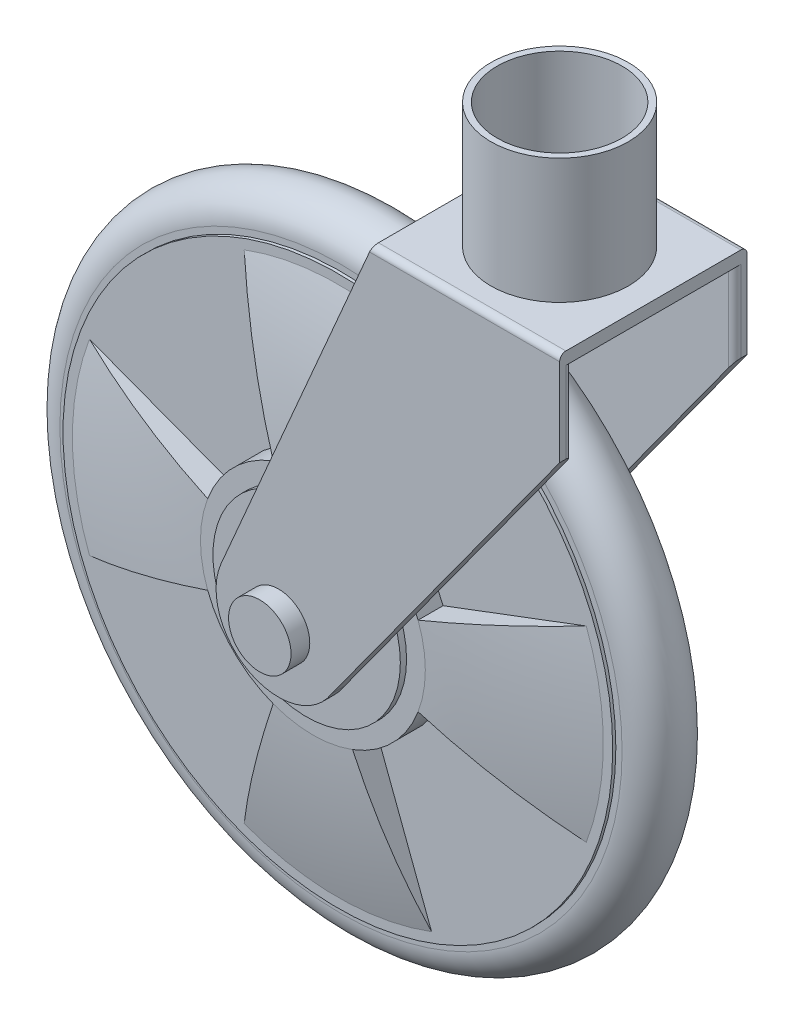
SolidWorks part; units mm, degrees
ref_plane "Plano frontal" through (0, 0, 0) normal (0, 0, 1) x (1, 0, 0)
ref_plane "Plano superior" through (0, 0, 0) normal (0, 1, 0) x (1, 0, 0)
ref_plane "Plano direito" through (0, 0, 0) normal (1, 0, 0) x (0, 0, -1)
sketch "Esboço1" plane through (0, 0, 0) normal (0, 1, 0) x (1, 0, 0)
  line L0 (0, 0) -> (-45, 0) construction
  line L1 (0, 0) -> (0, 36.2731) construction
  line L2 (-45, 5) -> (-44, 5)
  line L3 (-44, 5) -> (-44, 5.5)
  line L4 (-44, 5.5) -> (0, 5.5)
  line L5 (0, 5.5) -> (0, 0)
  line L6 (-45, -5) -> (-44, -5)
  line L7 (-44, -5) -> (-44, -5.5)
  line L8 (-44, -5.5) -> (0, -5.5)
  line L9 (0, 5.5) -> (0, -5.5)
  arc A0 (-45, 5) -> (-45, -5) centre (-45, 0) ccw
  point P7 (-44, 5.25)
  dimension "D1" = 10
  dimension "D2" = 45
  dimension "D3" = 0.5
  dimension "D4" = 1
revolve "Revolução3" add sketch "Esboço1" angle 360 about L1
sketch "Esboço3" plane through (0, 0, 5.5) normal (0, 0, 1) x (1, 0, 0)
  line L0 (0, 18) -> (0, 42.5) construction
  line L1 (-15, 39.7649) -> (-6.3529, 16.8416)
  line L2 (15, 39.7649) -> (6.3529, 16.8416)
  line L3 (39.7649, -15) -> (16.8416, -6.3529)
  line L4 (39.7649, 15) -> (16.8416, 6.3529)
  line L5 (-15, -39.7649) -> (-6.3529, -16.8416)
  line L6 (15, -39.7649) -> (6.3529, -16.8416)
  line L7 (-39.7649, 15) -> (-16.8416, 6.3529)
  line L8 (-39.7649, -15) -> (-16.8416, -6.3529)
  arc A0 (-16.8416, -6.3529) -> (-6.3529, -16.8416) centre (0, 0) ccw
  arc A1 (-39.7649, 15) -> (-39.7649, -15) centre (0, 0) ccw
  arc A2 (-15, -39.7649) -> (15, -39.7649) centre (0, 0) ccw
  arc A3 (15, 39.7649) -> (-15, 39.7649) centre (0, 0) ccw
  arc A4 (39.7649, -15) -> (39.7649, 15) centre (0, 0) ccw
  arc A5 (6.3529, -16.8416) -> (16.8416, -6.3529) centre (0, 0) ccw
  arc A6 (16.8416, 6.3529) -> (6.3529, 16.8416) centre (0, 0) ccw
  arc A7 (-6.3529, 16.8416) -> (-16.8416, 6.3529) centre (0, 0) ccw
  circle A8 centre (0, 0) radius 18 construction
  point P7 (0, 0)
  point P24 (0, 0)
  dimension "D1" = 36
  dimension "D2" = 85
  dimension "D3" = 15
  dimension "D4" = 4
extrude "Ressalto-extrusão1" add sketch "Esboço3" along normal blind 4
sketch "Esboço4" plane through (0, 0, 0) normal (1, 0, 0) x (0, 0, -1)
  line L0 (-5.5, 18) -> (-9.5, 18) construction
  line L1 (-5.5, 39.7649) -> (-5.5, 16.8416) construction
  line L2 (-5.5, 18) -> (-5.5, 42.5) construction
  line L3 (-5.5, 42.5) -> (-20.394, 42.5)
  line L4 (-5.5, 18) -> (-5.5, -18) construction
  line L5 (-9.5, 16.8416) -> (-9.5, 39.7649) construction
  line L6 (-20.394, 42.5) -> (-19.7205, 18)
  line L7 (-19.7205, 18) -> (-9.5, 18) construction
  line L8 (0, 0) -> (-37.0086, 0) construction
  line L9 (-9.5, 18) -> (-19.7205, 18)
  arc A0 (-9.5, 18) -> (-5.5, 42.5) centre (107.3195, 11.504) cw
revolve "Corte-Revolução1" cut sketch "Esboço4" angle 360 about L8
sketch "Esboço5" plane through (0, 0, 9.5) normal (0, 0, 1) x (1, 0, 0)
  circle A0 centre (0, 0) radius 15
  dimension "D1" = 30
extrude "Ressalto-extrusão2" add sketch "Esboço5" along normal blind 1
mirror "Espelhar1" about plane through (0, 0, 0) normal (0, 0, 1) of "Ressalto-extrusão2", "Corte-Revolução1", "Ressalto-extrusão1"
sketch "Esboço6" plane through (0, 0, 10.5) normal (0, 0, 1) x (1, 0, 0)
  circle A0 centre (0, 0) radius 5
  dimension "D1" = 10
extrude "Corte-extrusão1" cut sketch "Esboço6" against normal through all
sketch "Esboço17" plane through (0, 0, 0) normal (0, 0, 1) x (1, 0, 0)
  line L0 (0, 0) -> (0, 83.0608) construction
  line L1 (0, 0) -> (88.5459, 0) construction
  line L2 (15, 60) -> (45, 60)
  line L3 (45, 60) -> (45, 45)
  line L4 (45, 45) -> (8.5163, -5.2415)
  line L5 (-9.1816, 3.9621) -> (15, 60)
  arc A0 (-9.1816, 3.9621) -> (8.5163, -5.2415) centre (0, 0) ccw
  dimension "D1" = 20
  dimension "D2" = 60
  dimension "D3" = 45
  dimension "D4" = 15
  dimension "D5" = 30
extrude "Ressalto-extrusão11" add sketch "Esboço17" along normal mid plane 30 separate body
shell "Casca4" thickness 2 removed face at (-2.4732, -4.7559, 0) removed face at (2.9092, 31.981, 0) removed face at (45, 52.5, 0) removed face at (26.7581, 19.8792, 0)
sketch "Esboço18" plane through (0, 0, 15) normal (0, 0, 1) x (1, 0, 0)
  circle A0 centre (0, 0) radius 5
  dimension "D1" = 10
extrude "Corte-extrusão2" cut sketch "Esboço18" against normal blind 30
sketch "Esboço19" plane through (0, 0, 0) normal (0, 0, 1) x (1, 0, 0)
  circle A0 centre (0, 0) radius 5 construction
  circle A1 centre (0, 0) radius 5
extrude "Ressalto-extrusão12" add sketch "Esboço19" along normal mid plane 36 separate body
sketch "Esboço20" plane through (0, 60, 0) normal (0, 1, 0) x (1, 0, 0)
  line L0 (30, 15) -> (30, -15) construction
  line L1 (45, 15) -> (15, 15) construction
  line L2 (45, -15) -> (15, -15) construction
  circle A0 centre (30, 0) radius 10
  dimension "D1" = 20
extrude "Extrusão-Fina4" add sketch "Esboço20" along normal blind 20 separate body thin thin type one direction wall 1
combine bodies "Combinar1" operation type add bodies to combine 119 117
fillet "Filete1" radius 1 2 edges at (30, 60, -15) (30, 60, 15)
fillet "Filete2" radius 1 2 edges at (45, 51.5, -13) (45, 51.5, 13)
